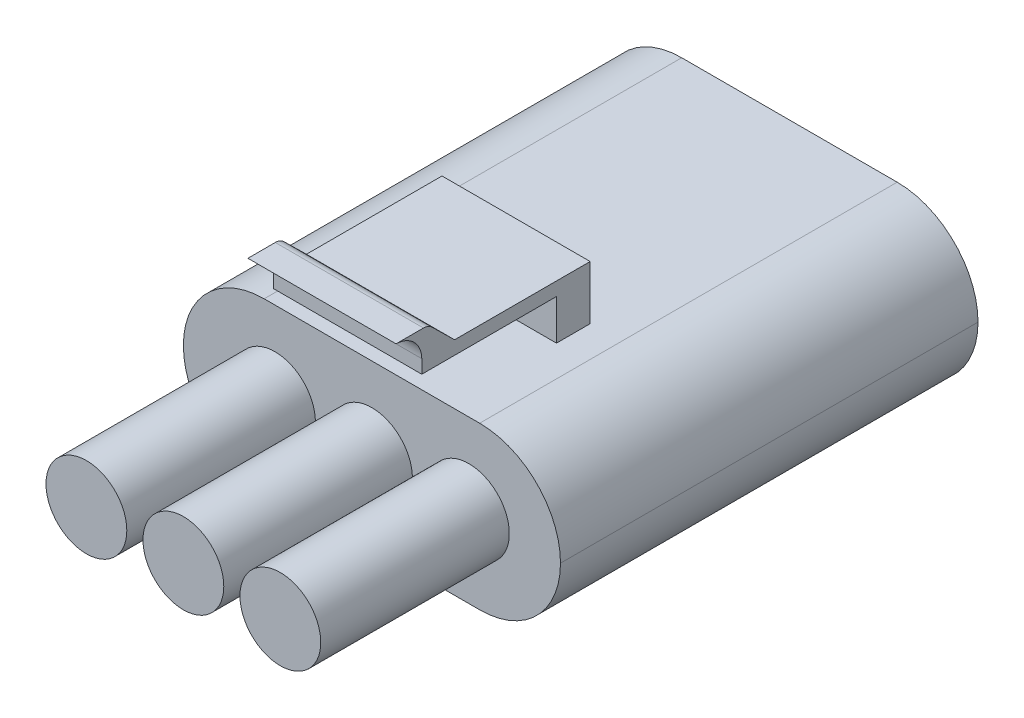
SolidWorks part; units mm, degrees
ref_plane "正面" through (0, 0, 0) normal (0, 0, 1) x (1, 0, 0)
ref_plane "平面" through (0, 0, 0) normal (0, 1, 0) x (1, 0, 0)
ref_plane "右側面" through (0, 0, 0) normal (1, 0, 0) x (0, 0, -1)
sketch "ｽｹｯﾁ1" plane through (0, 0, 0) normal (0, 0, 1) x (1, 0, 0)
  line L1 (0, 0) -> (28, 0)
  line L2 (0, 0) -> (0, 12)
  line L3 (0, 12) -> (28, 12)
  line L4 (28, 0) -> (28, 12)
  dimension "D1" = 28
  dimension "D2" = 12
extrude "ﾎﾞｽ - 押し出し1" add sketch "ｽｹｯﾁ1" along normal blind 31
fillet "ﾌｨﾚｯﾄ1" radius 6 4 edges at (28, 0, 15.5) (28, 12, 15.5) (0, 0, 15.5) (0, 12, 15.5)
sketch "ｽｹｯﾁ2" plane through (0, 0, 31) normal (0, 0, 1) x (1, 0, 0)
  line L0 (14, 12) -> (14, 0) construction
  line L1 (22, 12) -> (6, 12) construction
  line L2 (6, 0) -> (22, 0) construction
  line L3 (0, 6) -> (28, 6) construction
  circle A0 centre (14, 6) radius 3
  circle A1 centre (6.7994, 6) radius 3
  circle A2 centre (21.2006, 6) radius 3
  dimension "D1" = 6
extrude "ﾎﾞｽ - 押し出し2" add sketch "ｽｹｯﾁ2" along normal blind 14
sketch "ｽｹｯﾁ3" plane through (0, 12, 0) normal (0, 1, 0) x (1, 0, 0)
  line L0 (22, -31) -> (6, -31) construction
  line L1 (8.7026, -20.5) -> (19.7026, -20.5)
  line L2 (8.7026, -20.5) -> (8.7026, -23)
  line L3 (8.7026, -23) -> (19.7026, -23)
  line L4 (19.7026, -20.5) -> (19.7026, -23)
  dimension "D1" = 2.5
  dimension "D2" = 11
  dimension "D3" = 8
extrude "ﾎﾞｽ - 押し出し3" add sketch "ｽｹｯﾁ3" along normal blind 4
sketch "ｽｹｯﾁ4" plane through (0, 0, 23) normal (0, 0, 1) x (1, 0, 0)
  line L0 (19.7026, 16) -> (19.7026, 12) construction
  line L1 (8.7026, 16) -> (19.7026, 16)
  line L2 (8.7026, 16) -> (8.7026, 15)
  line L3 (8.7026, 15) -> (19.7026, 15)
  line L4 (19.7026, 16) -> (19.7026, 15)
  dimension "D1" = 1
extrude "ﾎﾞｽ - 押し出し4" add sketch "ｽｹｯﾁ4" along normal blind 10
sketch "ｽｹｯﾁ6" plane through (19.7026, 0, 0) normal (1, 0, 0) x (0, 0, -1)
  line L0 (-35.0017, 17.9128) -> (-32.8787, 17.9128)
  line L1 (-32.2475, 17.6544) -> (-30.566, 16)
  line L2 (-33, 16) -> (-30.566, 16)
  arc A0 (-33, 16) -> (-35.0017, 17.9128) centre (-34.9573, 15.9556) ccw
  arc A1 (-32.8787, 17.9128) -> (-32.2475, 17.6544) centre (-32.8787, 17.0128) cw
  line M3 (-20.5, 16) -> (-33, 16)
  dimension "D1" = 0.9
extrude "ﾎﾞｽ - 押し出し5" add sketch "ｽｹｯﾁ6" against normal blind 11 contours A1 L0 A0 L1 M3 region at (19.7026, 16.906, 32.4503)
sketch "ｽｹｯﾁ7" plane through (0, 0, 0) normal (0, 0, -1) x (-1, 0, 0)
  circle A0 centre (-14, 6.4473) radius 4.9855
extrude "ｶｯﾄ - 押し出し1" cut sketch "ｽｹｯﾁ7" against normal blind 1
